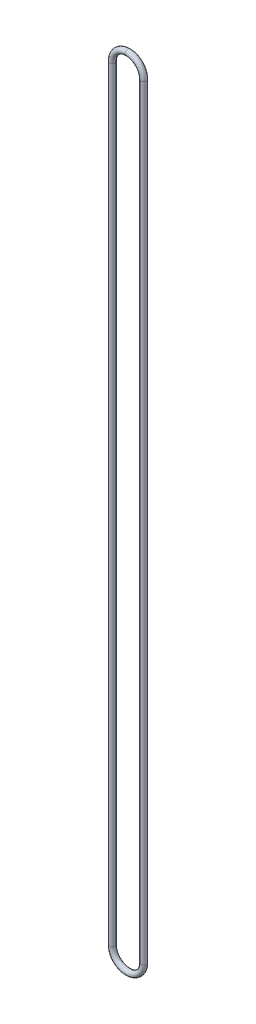
SolidWorks part; units mm, degrees
ref_plane "Front Plane" through (0, 0, 0) normal (0, 0, 1) x (1, 0, 0)
ref_plane "Top Plane" through (0, 0, 0) normal (0, 1, 0) x (1, 0, 0)
ref_plane "Right Plane" through (0, 0, 0) normal (1, 0, 0) x (0, 0, -1)
sketch "Sketch1" plane through (0, 0, 0) normal (0, 0, 1) x (1, 0, 0)
  line L0 (-17.4625, 850.9) -> (-17.4625, 0)
  line L1 (17.4625, 850.9) -> (17.4625, 0)
  circle A0 centre (0, 0) radius 17.4625 construction
  circle A1 centre (0, 850.9) radius 17.4625 construction
  arc A2 (-17.4625, 850.9) -> (17.4625, 850.9) centre (0, 850.9) cw
  arc A3 (-17.4625, 0) -> (17.4625, 0) centre (0, 0) ccw
  dimension "D2" = 17.4625
  dimension "D1" = 850.9
sketch "Sketch2" plane through (0, 0, 0) normal (1, 0, 0) x (0, 0, -1)
  circle A0 centre (0, 868.3625) radius 3.175
  dimension "D1" = 6.35
sweep "Sweep1" add profiles "Sketch2" path "Sketch1"
